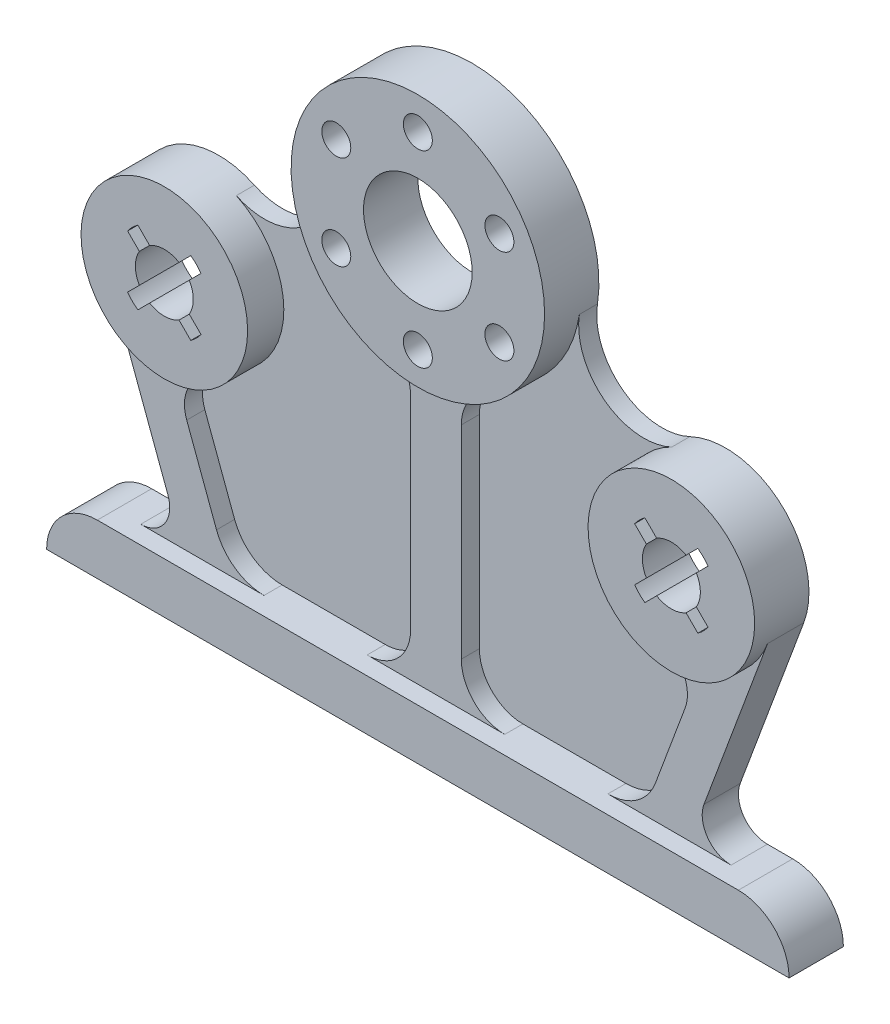
SolidWorks part; units mm, degrees
ref_plane "Спереди" through (0, 0, 0) normal (0, 0, 1) x (1, 0, 0)
ref_plane "Сверху" through (0, 0, 0) normal (0, 1, 0) x (1, 0, 0)
ref_plane "Справа" through (0, 0, 0) normal (1, 0, 0) x (0, 0, -1)
sketch "Эскиз1" plane through (0, 0, 0) normal (0, 0, 1) x (1, 0, 0)
  line L0 (0, 0) -> (0, 66.3129) construction
  line L1 (0, 0) -> (0, -149.8144) construction
  line L2 (-7, -42.9884) -> (-7, -99)
  line L3 (7, -42.9884) -> (7, -99)
  line L4 (102.5, -125) -> (-102.5, -125)
  line L5 (-88.5, -111) -> (88.5, -111)
  line L6 (-70, -45) -> (-70, -100.2121) construction
  line L7 (-70, -45) -> (-40.2927, -74.7073) construction
  line L8 (-62.6892, -55.1392) -> (-65.937, -51.8914)
  line L9 (-59.8608, -52.3108) -> (-63.1086, -49.063)
  line L10 (-80.1392, -52.3108) -> (-76.8914, -49.063)
  line L11 (-77.3108, -55.1392) -> (-74.063, -51.8914)
  line L12 (-77.3108, -34.8608) -> (-74.063, -38.1086)
  line L13 (-80.1392, -37.6892) -> (-76.8914, -40.937)
  line L14 (-59.8608, -37.6892) -> (-63.1086, -40.937)
  line L15 (-62.6892, -34.8608) -> (-65.937, -38.1086)
  line L16 (-91.5582, -53.0152) -> (-74.0108, -100.2121)
  line L17 (62.6892, -34.8608) -> (65.937, -38.1086)
  line L18 (59.8608, -37.6892) -> (63.1086, -40.937)
  line L19 (59.8608, -52.3108) -> (63.1086, -49.063)
  line L20 (62.6892, -55.1392) -> (65.937, -51.8914)
  line L21 (80.1392, -37.6892) -> (76.8914, -40.937)
  line L22 (77.3108, -34.8608) -> (74.063, -38.1086)
  line L23 (77.3108, -55.1392) -> (74.063, -51.8914)
  line L24 (80.1392, -52.3108) -> (76.8914, -49.063)
  line L26 (-68.8157, -79.7505) -> (-60.5886, -101.8788)
  line L27 (68.8157, -79.7505) -> (60.5886, -101.8788)
  line L29 (91.5582, -53.0152) -> (74.0108, -100.2121)
  circle A0 centre (0, 0) radius 35
  circle A1 centre (0, 0) radius 15
  circle A2 centre (0, 26) radius 4
  circle A3 centre (22.5167, 13) radius 4
  circle A4 centre (22.5167, -13) radius 4
  circle A5 centre (0, -26) radius 4
  circle A6 centre (-22.5167, -13) radius 4
  circle A7 centre (-22.5167, 13) radius 4
  arc A8 (-7, -42.9884) -> (-14.1489, -32.0126) centre (-19, -42.9884) ccw
  arc A9 (7, -42.9884) -> (14.1489, -32.0126) centre (19, -42.9884) cw
  arc A10 (-88.5, -111) -> (-102.5, -125) centre (-88.5, -125) ccw
  arc A11 (88.5, -111) -> (102.5, -125) centre (88.5, -125) cw
  arc A12 (-19, -111) -> (-7, -99) centre (-19, -99) ccw
  arc A13 (7, -99) -> (19, -111) centre (19, -99) ccw
  circle A14 centre (-70, -45) radius 23
  circle A15 centre (70, -45) radius 23
  arc A16 (-77.3108, -34.8608) -> (-80.1392, -37.6892) centre (-70, -45) ccw
  arc A17 (-65.937, -38.1086) -> (-74.063, -38.1086) centre (-70, -45) ccw
  arc A18 (-80.1392, -52.3108) -> (-77.3108, -55.1392) centre (-70, -45) ccw
  arc A19 (-59.8608, -37.6892) -> (-62.6892, -34.8608) centre (-70, -45) ccw
  arc A20 (-62.6892, -55.1392) -> (-59.8608, -52.3108) centre (-70, -45) ccw
  arc A21 (-74.063, -51.8914) -> (-65.937, -51.8914) centre (-70, -45) ccw
  arc A22 (-63.1086, -49.063) -> (-63.1086, -40.937) centre (-70, -45) ccw
  arc A23 (-76.8914, -40.937) -> (-76.8914, -49.063) centre (-70, -45) ccw
  arc A24 (65.937, -38.1086) -> (74.063, -38.1086) centre (70, -45) cw
  arc A25 (63.1086, -49.063) -> (63.1086, -40.937) centre (70, -45) cw
  arc A26 (74.063, -51.8914) -> (65.937, -51.8914) centre (70, -45) cw
  arc A27 (62.6892, -55.1392) -> (59.8608, -52.3108) centre (70, -45) cw
  arc A28 (76.8914, -40.937) -> (76.8914, -49.063) centre (70, -45) cw
  arc A29 (80.1392, -52.3108) -> (77.3108, -55.1392) centre (70, -45) cw
  arc A30 (77.3108, -34.8608) -> (80.1392, -37.6892) centre (70, -45) cw
  arc A31 (-60.1252, -24.2277) -> (-34.6019, -5.2639) centre (-52.3972, -7.9711) ccw
  arc A32 (60.1252, -24.2277) -> (34.6019, -5.2639) centre (52.3972, -7.9711) cw
  arc A33 (-62.6418, -66.7912) -> (-68.8157, -79.7505) centre (-59.4426, -76.2657) ccw
  arc A34 (-81.5093, -111) -> (-74.0108, -100.2121) centre (-81.5093, -103) ccw
  arc A35 (-60.5886, -101.8788) -> (-47.4662, -111) centre (-47.4662, -97) ccw
  arc A36 (60.5886, -101.8788) -> (47.4662, -111) centre (47.4662, -97) cw
  arc A37 (81.5093, -111) -> (74.0108, -100.2121) centre (81.5093, -103) cw
  arc A38 (62.6418, -66.7912) -> (68.8157, -79.7505) centre (59.4426, -76.2657) cw
  arc A39 (59.8608, -37.6892) -> (62.6892, -34.8608) centre (70, -45) cw
  point P19 (0, 0)
  point P30 (0, -125)
  point P37 (0, -111)
  point P58 (-70, -45)
  point P67 (-70, -45)
  point P80 (-70, -45)
  dimension "D1" = 70
  dimension "D2" = 30
  dimension "D3" = 8
  dimension "D7" = 12
  dimension "D9" = 14
  dimension "D11" = 12
  dimension "D12" = 12
  dimension "D13" = 46
  dimension "D20" = 4
  dimension "D22" = 10
  dimension "D18" = 16
  dimension "D17" = 25
  dimension "D21" = 18
  dimension "D24" = 8
  dimension "D25" = 14
  dimension "D4" = 26
  dimension "D6" = 7
  dimension "D8" = 205
  dimension "D10" = 125
  dimension "D14" = 45
  dimension "D15" = 70
  dimension "D16" = 45
  dimension "D19" = 2
  dimension "D23" = 12
  dimension "D26" = 148.0217
  dimension "D5" = 6
extrude "Бобышка-Вытянуть1" add sketch "Эскиз1" along normal blind 5 contours A38 A15 A32 A0 A9 L3 A13 L5 A36 L27 | L26 A35 L5 A12 L2 A8 A0 A31 A14 A33 region at (-33.6229, -69.8214, 0) region at (33.6229, -69.8214, 0)
extrude "Бобышка-Вытянуть2" add sketch "Эскиз1<3>" along normal blind 15 contours A0 A7 A6 A5 A4 A3 A2 A1 | A14 A23 L13 A16 L12 A17 L15 A19 L14 A22 L9 A20 L8 A21 L11 A18 L10 | A15 L18 A39 L17 A24 L22 A30 L21 A28 L24 A29 L23 A26 L20 A27 L19 A25 | A11 L5 A10 L4 region at (-27.0171, -20.6582, 0) region at (0, -118.1169, 0) region at (-51.1062, -33.0617, 0) region at (81.9383, -26.1062, 0)
sketch "Эскиз1<3>" plane through (0, 0, 0) normal (0, 0, 1) x (1, 0, 0) same geometry as "Эскиз1"
extrude "Бобышка-Вытянуть3" add sketch "Эскиз1<4>" along normal blind 10 contours A35 L26 A33 A14 L16 A34 L5 | A13 L3 A9 A0 A8 L2 A12 L5 | A15 A38 L27 A36 L5 A37 L29 region at (0, -73.9578, 0) region at (-72.0302, -88.2932, 0) region at (72.0302, -88.2932, 0)
sketch "Эскиз1<4>" plane through (0, 0, 0) normal (0, 0, 1) x (1, 0, 0) same geometry as "Эскиз1"
